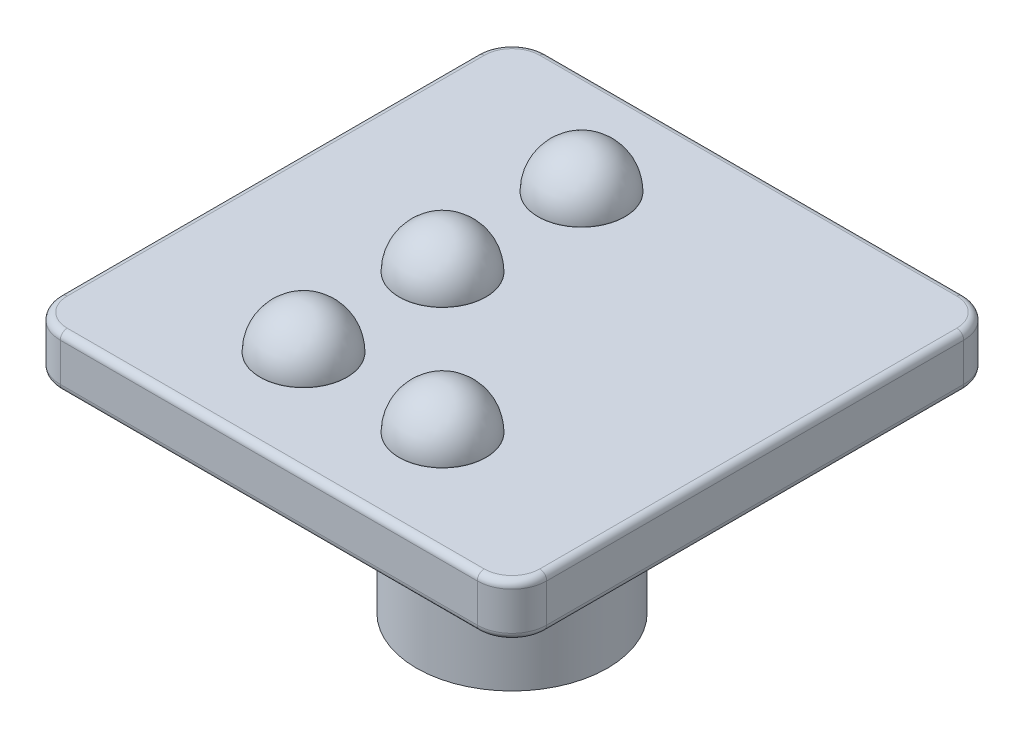
SolidWorks part; units mm, degrees
ref_plane "Front Plane" through (0, 0, 0) normal (0, 0, 1) x (1, 0, 0)
ref_plane "Top Plane" through (0, 0, 0) normal (0, 1, 0) x (1, 0, 0)
ref_plane "Right Plane" through (0, 0, 0) normal (1, 0, 0) x (0, 0, -1)
sketch "Sketch1" plane through (0, 0, 0) normal (0, 1, 0) x (1, 0, 0)
  line L1 (-7.3247, 4.3967) -> (4.6753, 4.3967)
  line L2 (-8.3247, 3.3967) -> (-8.3247, -8.6033)
  line L3 (-7.3247, -9.6033) -> (4.6753, -9.6033)
  line L4 (5.6753, 3.3967) -> (5.6753, -8.6033)
  arc A0 (-8.3247, -8.6033) -> (-7.3247, -9.6033) centre (-7.3247, -8.6033) ccw
  arc A1 (4.6753, -9.6033) -> (5.6753, -8.6033) centre (4.6753, -8.6033) ccw
  arc A2 (4.6753, 4.3967) -> (5.6753, 3.3967) centre (4.6753, 3.3967) cw
  arc A3 (-7.3247, 4.3967) -> (-8.3247, 3.3967) centre (-7.3247, 3.3967) ccw
  point P8 (5.6753, -9.6033)
  point P11 (5.6753, 4.3967)
  point P14 (-8.3247, 4.3967)
  dimension "D3" = 1
  dimension "D1" = 14
  dimension "D2" = 14
extrude "Boss-Extrude1" add sketch "Sketch1" along normal blind 1.5
sketch "Sketch2" plane through (0, 0, 0) normal (0, -1, 0) x (1, 0, 0)
  line L0 (-7.3247, 9.6033) -> (4.6753, 9.6033) construction
  line L1 (5.6753, 8.6033) -> (5.6753, -3.3967) construction
  line L2 (-1.3247, -4.3967) -> (-1.3247, 9.6033) construction
  line L3 (-8.3247, 2.6033) -> (5.6753, 2.6033) construction
  line L4 (-8.3247, -3.3967) -> (-8.3247, 8.6033) construction
  circle A0 centre (-1.3247, 2.6033) radius 2.75
  dimension "D1" = 7
  dimension "D2" = 7
extrude "Boss-Extrude2" add sketch "Sketch2" along normal blind 6
sketch "Sketch3" plane through (0, -6, 0) normal (0, -1, 0) x (1, 0, 0)
  line L0 (-1.3247, 5.3533) -> (-1.3247, -0.1467) construction
  line L1 (-3.3247, 3.1533) -> (0.6753, 3.1533)
  line L2 (-3.3247, 3.1533) -> (-3.3247, 2.0533)
  line L3 (-3.3247, 2.0533) -> (0.6753, 2.0533)
  line L4 (0.6753, 3.1533) -> (0.6753, 2.0533)
  line L5 (-1.8747, 4.6033) -> (-0.7747, 4.6033)
  line L6 (-1.8747, 4.6033) -> (-1.8747, 0.6033)
  line L7 (-1.8747, 0.6033) -> (-0.7747, 0.6033)
  line L8 (-0.7747, 4.6033) -> (-0.7747, 0.6033)
  line L9 (-4.0747, 2.6033) -> (1.4253, 2.6033) construction
  circle A3 centre (-1.3247, 2.6033) radius 2.75 construction
  circle A4 centre (-1.3247, 2.6033) radius 2.75 construction
  dimension "D7" = 0.55
  dimension "D1" = 4
  dimension "D2" = 1.1
  dimension "D3" = 1.1
  dimension "D4" = 4
  dimension "D8" = 0.55
extrude "Cut-Extrude1" cut sketch "Sketch3" against normal blind 6 contours L8 L5 L6 L1 | L1 L8 L3 L4 | L8 L1 L6 L3 | L6 L1 L2 L3 | L8 L3 L6 L7 region at (-2.5997, -6, 2.6033) region at (-1.3247, -6, 3.8783) region at (-1.3247, -6, 2.6033) region at (-0.0497, -6, 2.6033) region at (-1.3247, -6, 1.3283)
chamfer "Chamfer1" distance 0.3 angle 45 12 edges at (-1.3247, -6, 0.6033) (-1.8747, -6, 1.3283) (-2.5997, -6, 2.0533) (-3.3247, -6, 2.6033) (-2.5997, -6, 3.1533) (-0.7747, -6, 1.3283) (-0.0497, -6, 2.0533) (0.6753, -6, 2.6033) (-0.0497, -6, 3.1533) (-0.7747, -6, 3.8783) (-1.3247, -6, 4.6033) (-1.8747, -6, 3.8783)
fillet "Fillet1" radius 1 1 edges at (-1.3247, 0, -0.1467)
sketch "Sketch4" plane through (0, 1.5, 0) normal (0, 1, 0) x (1, 0, 0)
  line L0 (-1.3247, 4.3967) -> (-1.3247, -9.6033) construction
  line L1 (4.6753, 4.3967) -> (-7.3247, 4.3967) construction
  line L2 (-7.3247, -9.6033) -> (4.6753, -9.6033) construction
  line L3 (5.6753, -2.6033) -> (-8.3247, -2.6033) construction
  line L4 (-8.3247, 3.3967) -> (-8.3247, -8.6033) construction
  line L5 (5.6753, -8.6033) -> (5.6753, 3.3967) construction
  line L6 (-3.3247, 4.3967) -> (-3.3247, -9.6033) construction
  line L7 (0.6753, 4.3967) -> (0.6753, -9.6033) construction
  line L8 (-8.3247, 1.3967) -> (5.6753, 1.3967) construction
  line L9 (5.6753, -6.6033) -> (-8.3247, -6.6033) construction
  circle A0 centre (-3.3247, 1.3967) radius 1.25
  circle A2 centre (-3.3247, -2.6033) radius 1.25
  circle A3 centre (-3.3247, -6.6033) radius 1.25
  circle A4 centre (0.6753, -6.6033) radius 1.25
  dimension "D1" = 4
  dimension "D2" = 4
  dimension "D3" = 2
  dimension "D4" = 2
extrude "Boss-Extrude3" add sketch "Sketch4" along normal blind 0.01
dome "Dome1" faces to dome 1 distance 1.25 reverse direction no elliptical dome no face at (-3.3247, 1.51, -0.1467) parameters "D1"=1.25
dome "Dome3" faces to dome 1 distance 1.25 reverse direction no elliptical dome no face at (-3.3247, 1.51, 3.8533) parameters "D1"=1.25
dome "Dome5" faces to dome 1 distance 1.25 reverse direction no elliptical dome no face at (-3.3247, 1.51, 7.8533) parameters "D1"=1.25
dome "Dome6" faces to dome 1 distance 1.25 reverse direction no elliptical dome no face at (0.6753, 1.51, 7.8533) parameters "D1"=1.25
fillet "Fillet3" radius 0.2 16 edges at (5.3824, 1.5, -4.1038) (5.6753, 1.5, 2.6033) (5.3824, 1.5, 9.3104) (-1.3247, 1.5, 9.6033) (-8.0318, 1.5, 9.3104) (-8.0318, 1.5, -4.1038) (-8.3247, 1.5, 2.6033) (-1.3247, 1.5, -4.3967) (5.3824, 0, 9.3104) (5.6753, 0, 2.6033) (5.3824, 0, -4.1038) (-1.3247, 0, -4.3967) (-8.0318, 0, -4.1038) (-8.3247, 0, 2.6033) (-8.0318, 0, 9.3104) (-1.3247, 0, 9.6033)
